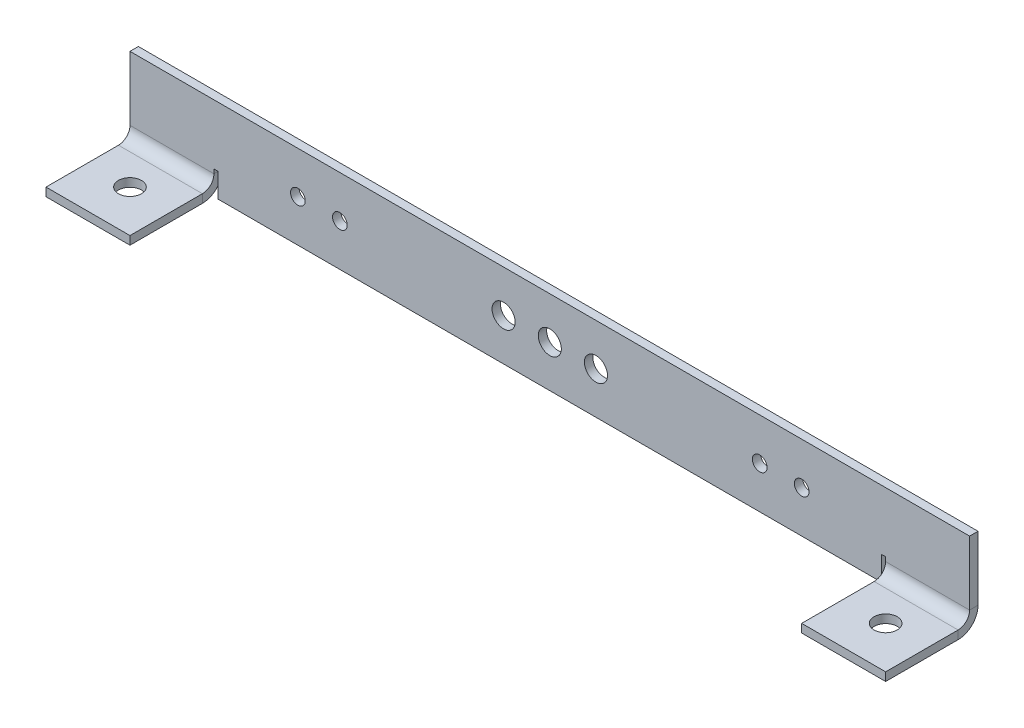
SolidWorks part; units mm, degrees
note: The reader was unsure of these and kept them because the rebuilt part matched: flange length of "边线-法兰1".
ref_plane "前视基准面" through (0, 0, 0) normal (0, 0, 1) x (1, 0, 0)
ref_plane "上视基准面" through (0, 0, 0) normal (0, 1, 0) x (1, 0, 0)
ref_plane "右视基准面" through (0, 0, 0) normal (1, 0, 0) x (0, 0, -1)
sketch "草图1" plane through (0, 0, 0) normal (0, 0, 1) x (1, 0, 0)
  line L0 (0, 0) -> (0, 58.0468) construction
  line L1 (-100, -20) -> (-100, 0)
  line L2 (100, -20) -> (100, 0)
  line L3 (-100, 0) -> (100, 0)
  line L5 (0, 0) -> (100, 0) construction
  line L9 (100, -20) -> (-100, -20)
  point P13 (0, -20)
  dimension "D1" = 20
  dimension "D3" = 100
base flange "基体-法兰1" sketch "草图1" thickness 2 reverse thickness direction no parameters "D1"=2.7366
edge flange "边线-法兰1" sketch "草图8" flange angle 90 flange length 22 flange position material inside bend radius 2.7366 thickness 2 relief rectangular parameters "D6"=10
sketch "草图8" plane through (0, -20, 0) normal (0, 1, 0) x (-1, 0, 0)
  line L2 (80, 0) -> (80, 20)
  line L3 (80, 20) -> (100, 20)
  line L4 (100, 20) -> (100, 0)
  line L10 (100, 0) -> (-100, 0) construction
  line L11 (100, 0) -> (80, 0)
  dimension "D1" = 20
  dimension "D2" = 20
bend "边线折弯1" bend radius 2.7366 bend angle 90 parameters "D5"=1
sketch "草图10" plane through (0, -18, 0) normal (0, 1, 0) x (1, 0, 0)
  line L0 (-100, -20) -> (-80, -20) construction
  line L1 (-80, -20) -> (-80, -2.7366) construction
  circle A0 centre (-90, -10) radius 2.75
  dimension "D3" = 5.5
  dimension "D1" = 10
  dimension "D2" = 10
extrude "切除-拉伸2" cut sketch "草图10" against normal blind 10 normal cut yes
mirror "镜向1" about plane through (0, 0, 0) normal (1, 0, 0) of "切除-拉伸2", "边线-法兰1"
bend "镜向折弯1" bend radius 2.7366 bend angle 90 parameters "D5"=2
sketch "草图11" plane through (0, 0, -2) normal (0, 0, -1) x (-1, 0, 0)
  line L0 (0, -10) -> (0, -20) construction
  line L1 (79, -20) -> (-79, -20) construction
  line L2 (-100, 0) -> (100, 0) construction
  line L3 (-100, -15.2634) -> (-100, 0) construction
  circle A0 centre (0, -10) radius 2.75
  circle A1 centre (-11, -10) radius 2.75
  circle A2 centre (11, -10) radius 2.75
  circle A3 centre (-60, -10) radius 1.75
  circle A4 centre (-50, -10) radius 1.75
  circle A5 centre (60, -10) radius 1.75
  circle A6 centre (50, -10) radius 1.75
  dimension "D1" = 5.5
  dimension "D4" = 3.5
  dimension "D6" = 40
  dimension "D2" = 10
  dimension "D3" = 11
  dimension "D5" = 2
extrude "切除-拉伸3" cut sketch "草图11" against normal blind 10 normal cut yes
sketch "折弯-线1" plane through (0, 0, 0) normal (0, 1, 0) x (1, 0, 0)
sketch "边界框1" plane through (0, 0, 0) normal (0, 1, 0) x (1, 0, 0)
sheet metal parameters "钣金6" thickness 2 parameters "D1"=2.7366
flat pattern "平板型式6" [suppressed]
sketch "折弯-线2" plane through (0, 0, 0) normal (0, 1, 0) x (1, 0, 0)
sketch "边界框2" [suppressed] plane through (0, 0, 0) normal (0, 1, 0) x (1, 0, 0)
sheet metal parameters "钣金7" thickness 2 parameters "D1"=2.7366
flat pattern "平板型式6" [suppressed]
sketch "折弯-线2" plane through (0, 0, 0) normal (0, 1, 0) x (1, 0, 0)
sketch "边界框2" [suppressed] plane through (0, 0, 0) normal (0, 1, 0) x (1, 0, 0)
bend of the flat pattern "展开-<边线折弯1>1"
sheet metal parameters "钣金8" thickness 2 parameters "D1"=2.7366
flat pattern "平板型式6" [suppressed]
sketch "折弯-线2" plane through (0, 0, 0) normal (0, 1, 0) x (1, 0, 0)
sketch "边界框2" [suppressed] plane through (0, 0, 0) normal (0, 1, 0) x (1, 0, 0)
bend of the flat pattern "展开-<边线折弯1>1"
bend of the flat pattern "展开-<镜向折弯1>1"
sheet metal parameters "钣金10" thickness 2 parameters "D1"=2.7366
flat pattern "平板型式6" [suppressed]
sketch "折弯-线2" plane through (0, 0, 0) normal (0, 1, 0) x (1, 0, 0)
sketch "边界框2" [suppressed] plane through (0, 0, 0) normal (0, 1, 0) x (1, 0, 0)
bend of the flat pattern "展开-<边线折弯1>1"
sheet metal parameters "钣金11" thickness 2 parameters "D1"=2.7366
flat pattern "平板型式6" [suppressed]
sketch "折弯-线2" plane through (0, 0, 0) normal (0, 1, 0) x (1, 0, 0)
sketch "边界框2" [suppressed] plane through (0, 0, 0) normal (0, 1, 0) x (1, 0, 0)
bend of the flat pattern "展开-<边线折弯1>1"
bend of the flat pattern "展开-<镜向折弯1>1"
